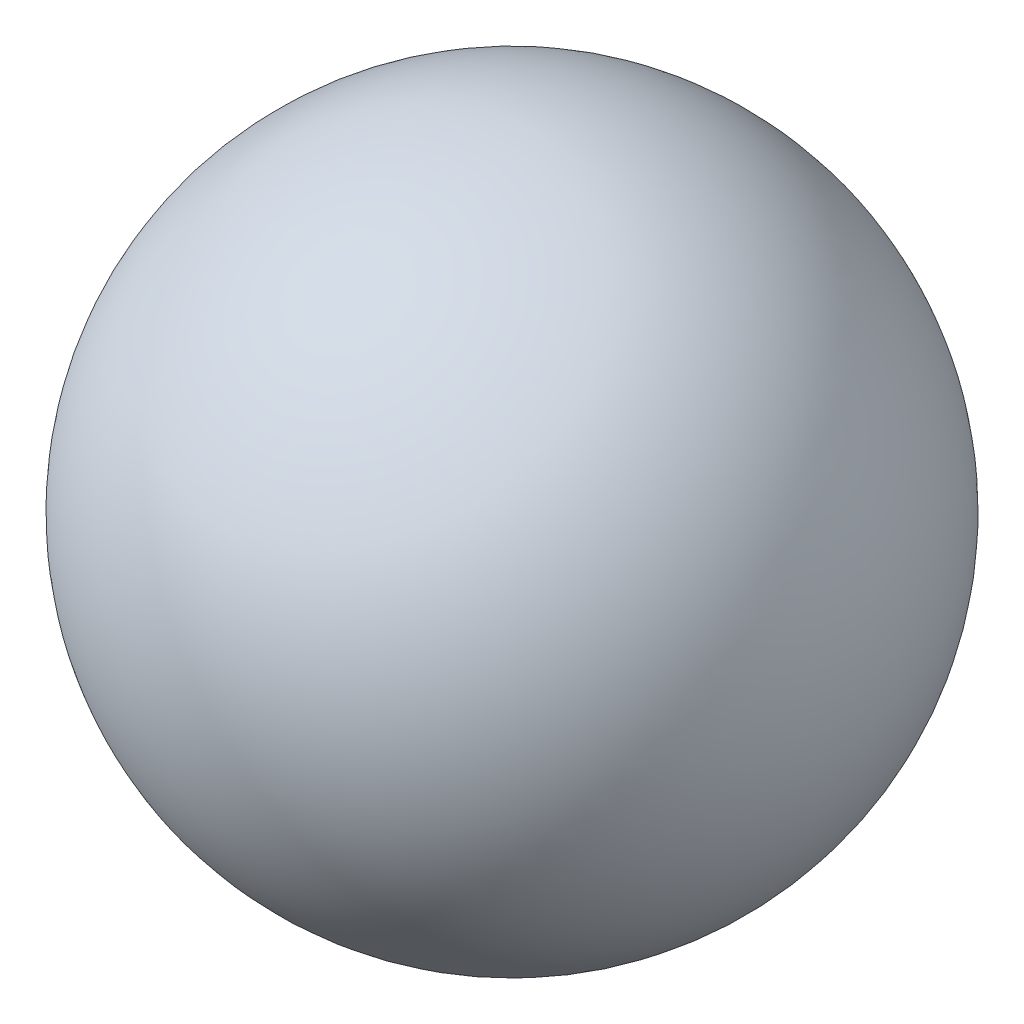
SolidWorks part; units mm, degrees
ref_plane "Front Plane" through (0, 0, 0) normal (0, 0, 1) x (1, 0, 0)
ref_plane "Top Plane" through (0, 0, 0) normal (0, 1, 0) x (1, 0, 0)
ref_plane "Right Plane" through (0, 0, 0) normal (1, 0, 0) x (0, 0, -1)
sketch "Sketch1" plane through (0, 0, 0) normal (0, 1, 0) x (1, 0, 0)
  line L0 (0, -260) -> (0, 260) construction
  line L1 (0, -140) -> (0, -260)
  line L2 (0, 140) -> (0, 260)
  circle A0 centre (0, 0) radius 140 construction
  circle A1 centre (0, 0) radius 260 construction
  arc A2 (0, 140) -> (0, -140) centre (0, 0) cw
  arc A3 (0, 260) -> (0, -260) centre (0, 0) cw
  dimension "D1" = 280
  dimension "D2" = 520
revolve "Revolve1" add sketch "Sketch1" angle 360 about L0
ref_axis "Axis1" through (0, 0, 544.3871) along (0, 0, -1)
